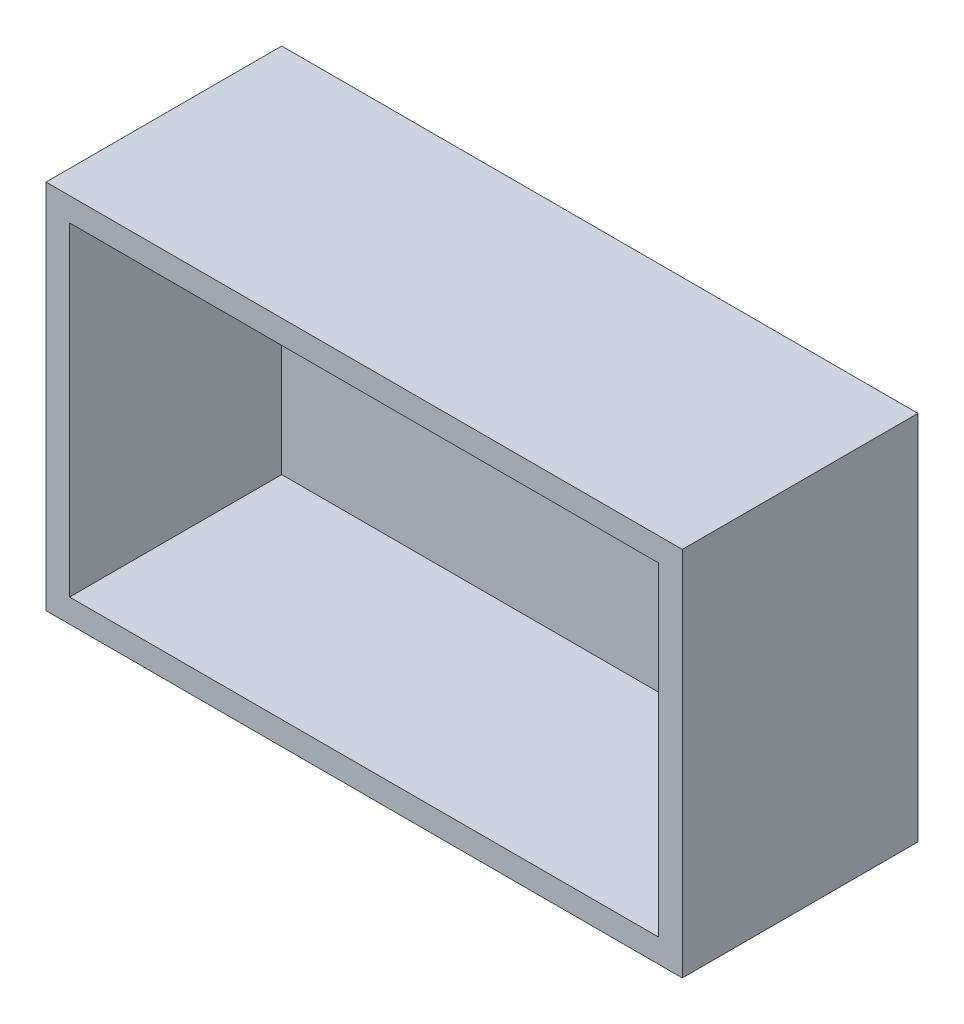
SolidWorks part; units mm, degrees
ref_plane "Front Plane" through (0, 0, 0) normal (0, 0, 1) x (1, 0, 0)
ref_plane "Top Plane" through (0, 0, 0) normal (0, 1, 0) x (1, 0, 0)
ref_plane "Right Plane" through (0, 0, 0) normal (1, 0, 0) x (0, 0, -1)
sketch "Sketch3" plane through (0, 0, 0) normal (0, 0, 1) x (1, 0, 0)
  line L1 (0, 0) -> (54, 0)
  line L2 (0, 0) -> (0, 31.5)
  line L3 (0, 31.5) -> (54, 31.5)
  line L4 (54, 0) -> (54, 31.5)
  dimension "D1" = 31.5
  dimension "D2" = 54
extrude "Boss-Extrude1" add sketch "Sketch3" along normal blind 20 contours L2 L1 L4 L3
shell "Shell7" thickness 2 removed face at (27, 15.75, 20)
